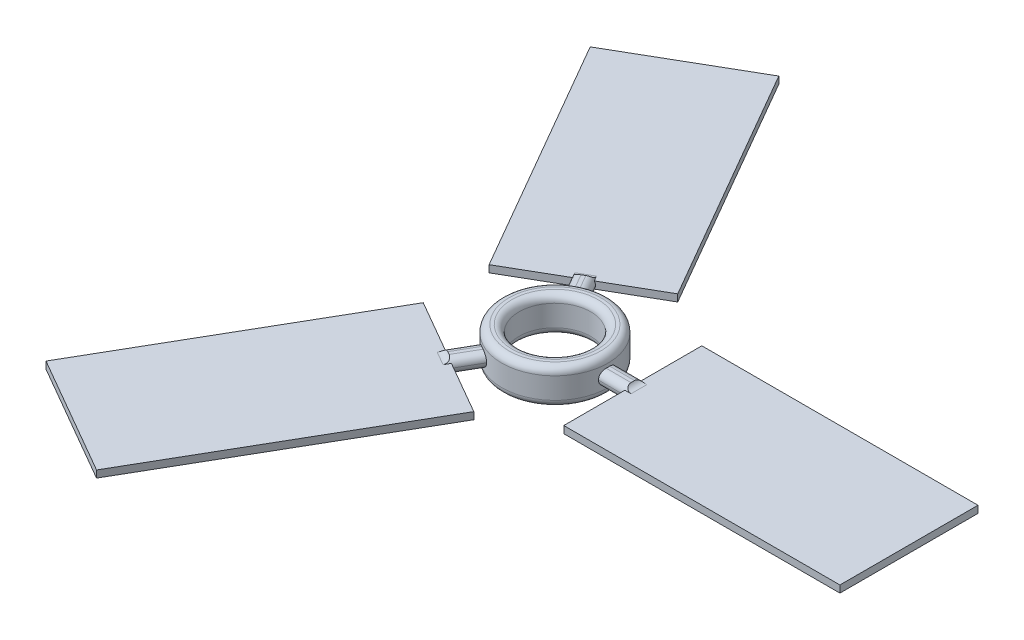
SolidWorks part; units mm, degrees
ref_plane "Front Plane" through (0, 0, 0) normal (0, 0, 1) x (1, 0, 0)
ref_plane "Top Plane" through (0, 0, 0) normal (0, 1, 0) x (1, 0, 0)
ref_plane "Right Plane" through (0, 0, 0) normal (1, 0, 0) x (0, 0, -1)
sketch "Sketch2" plane through (0, 0, 0) normal (0, 1, 0) x (1, 0, 0)
  line L0 (0, 0) -> (15, 0) construction
  line L1 (0, 0) -> (-7.5, 12.9904) construction
  line L2 (0, 0) -> (-7.5, -12.9904) construction
  line L3 (15, 0) -> (100, 0) construction
  line L4 (-7.5, 12.9904) -> (-50, 86.6025) construction
  line L5 (-7.5, -12.9904) -> (-50, -86.6025) construction
  line L6 (-27.8875, 9.3026) -> (5.8875, 28.8026)
  line L7 (100, -19.5) -> (22, -19.5)
  line L8 (100, -19.5) -> (100, 19.5)
  line L9 (100, 19.5) -> (22, 19.5)
  line L10 (22, -19.5) -> (22, 19.5)
  line L11 (5.8875, 28.8026) -> (-33.1125, 96.3525)
  line L12 (-33.1125, 96.3525) -> (-66.8875, 76.8525)
  line L13 (-66.8875, 76.8525) -> (-27.8875, 9.3026)
  line L14 (-33.1125, -96.3525) -> (-66.8875, -76.8525)
  line L19 (-33.1125, -96.3525) -> (5.8875, -28.8026)
  line L20 (-66.8875, -76.8525) -> (-27.8875, -9.3026)
  line L21 (5.8875, -28.8026) -> (-27.8875, -9.3026)
  line L22 (14.7902, -2.5) -> (22, -2.5)
  line L23 (14.7902, 2.5) -> (22, 2.5)
  line L24 (-9.5602, -11.5587) -> (-13.1651, -17.8026)
  line L25 (-5.23, -14.0587) -> (-8.8349, -20.3026)
  line L26 (-5.23, 14.0587) -> (-8.8349, 20.3026)
  line L27 (-9.5602, 11.5587) -> (-13.1651, 17.8026)
  circle A0 centre (0, 0) radius 15
  circle A1 centre (0, 0) radius 10.13
  circle A2 centre (0, 0) radius 15
  circle A3 centre (0, 0) radius 15
  point P14 (22, 0)
  point P19 (-11, 19.0526)
  point P20 (-50, -86.6025)
  point P24 (-50, 86.6025)
  point P27 (-11, -19.0526)
  point P43 (0, 0)
  dimension "D1" = 30
  dimension "D2" = 4.87
  dimension "D3" = 120
  dimension "D4" = 120
  dimension "D5" = 85
  dimension "D6" = 85
  dimension "D7" = 85
  dimension "D8" = 39
  dimension "D9" = 78
  dimension "D10" = 78
  dimension "D11" = 39
  dimension "D12" = 78
  dimension "D13" = 39
  dimension "D14" = 5
  dimension "D15" = 3
extrude "Boss-Extrude2" add sketch "Sketch2" along normal blind 5 and the other way blind 5 contours A0 A1 region at (-7.2879, 0, -12.623)
extrude "Boss-Extrude3" add sketch "Sketch2<3>" along normal blind 2 and the other way blind 2 contours A0 L24 L21 L25 | A0 L22 L10 L23 | A0 L26 L6 L27 region at (-9.2324, 0, -15.991) region at (-9.2324, 0, 15.991) region at (18.4649, 0, 0)
sketch "Sketch2<3>" plane through (0, 0, 0) normal (0, 1, 0) x (1, 0, 0) same geometry as "Sketch2"
extrude "Boss-Extrude4" add sketch "Sketch2<4>" along normal blind 1 and the other way blind 1 contours L12 L13 L6 L11 | L19 L21 L20 L14 | L10 L7 L8 L9 region at (-30.5, 0, -52.8275) region at (-30.5, 0, 52.8275) region at (61, 0, 0)
sketch "Sketch2<4>" plane through (0, 0, 0) normal (0, 1, 0) x (1, 0, 0) same geometry as "Sketch2"
fillet "Fillet1" radius 2 2 edges at (0, -5, 15) (0, 5, 15)
fillet "Fillet2" radius 2 2 edges at (0, 5, 10.13) (0, -5, 10.13)
fillet "Fillet4" radius 2 12 edges at (-7.0325, 2, 17.1806) (-11.3626, 2, 14.6806) (-7.0325, 2, -17.1806) (-11.3626, 2, -14.6806) (18.3951, 2, 2.5) (18.3951, 2, -2.5) (18.3951, -2, -2.5) (18.3951, -2, 2.5) (-11.3626, -2, 14.6806) (-7.0325, -2, 17.1806) (-11.3626, -2, -14.6806) (-7.0325, -2, -17.1806)
fillet "Fillet5" radius 2 6 edges at (22, -1, 0) (-11, -1, 19.0526) (-11, -1, -19.0526) (22, 1, 0) (-11, 1, -19.0526) (-11, 1, 19.0526)
